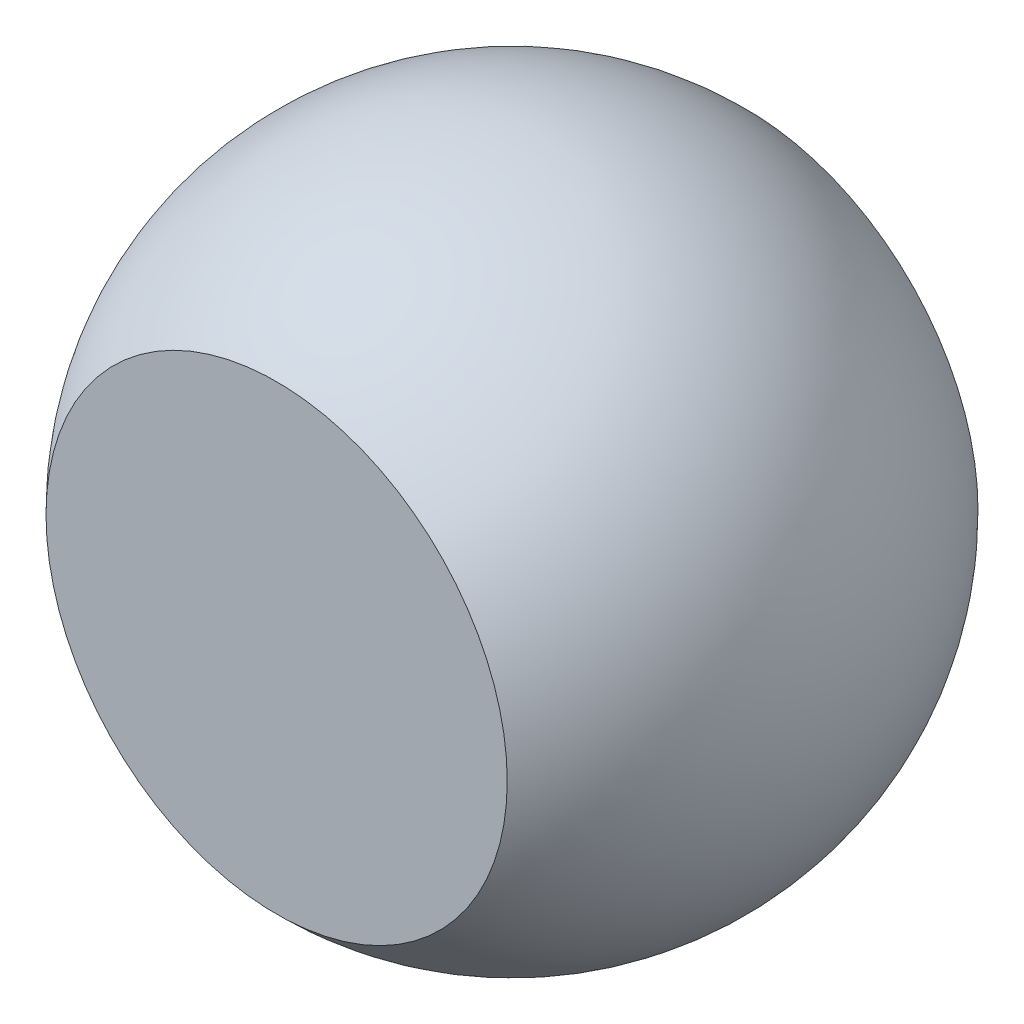
SolidWorks part; units mm, degrees
ref_plane "Front Plane" through (0, 0, 0) normal (0, 0, 1) x (1, 0, 0)
ref_plane "Top Plane" through (0, 0, 0) normal (0, 1, 0) x (1, 0, 0)
ref_plane "Right Plane" through (0, 0, 0) normal (1, 0, 0) x (0, 0, -1)
sketch "Sketch1" plane through (0, 0, 0) normal (0, 1, 0) x (1, 0, 0)
  line L0 (0, 0.35) -> (0, -0.35)
  arc A0 (0, 0.35) -> (0, -0.35) centre (0, 0) ccw
  dimension "D1" = 0.7
revolve "Revolve3" add sketch "Sketch1" angle 360 about L0
sketch "Sketch2" plane through (0, 0, 0) normal (1, 0, 0) x (0, 0, -1)
  line L0 (0, 0.385) -> (0, -0.385) construction
  line L1 (0.25, 0.6105) -> (0.45, 0.6105)
  line L2 (0.25, 0.6105) -> (0.25, -0.623)
  line L3 (0.25, -0.623) -> (0.45, -0.623)
  line L4 (0.45, 0.6105) -> (0.45, -0.623)
  dimension "D1" = 0.25
  dimension "D2" = 0.2
extrude "Cut-Extrude1" cut sketch "Sketch2" against normal mid plane 10
mirror "Mirror1" about plane through (0, 0, 0) normal (0, 0, 1) of "Cut-Extrude1"
ref_axis "Axis2" through (0, 0, -0.7151) along (0, 0, 1)
